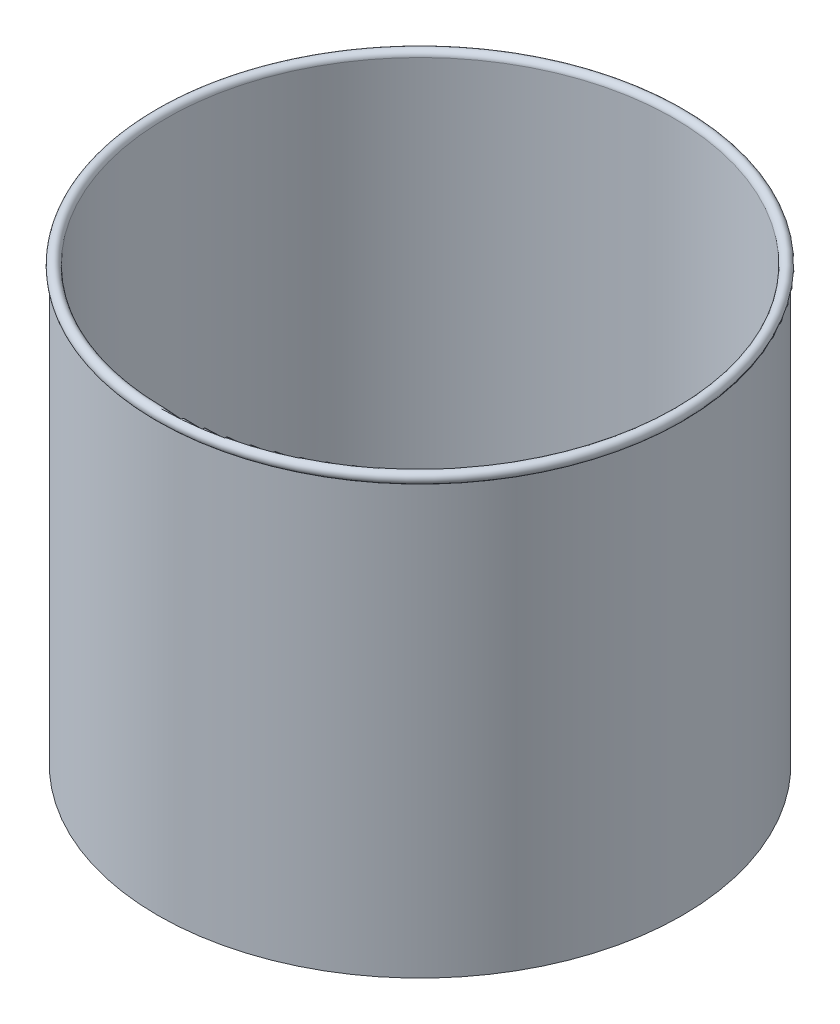
SolidWorks part; units mm, degrees
material "1023 Carbon Steel Sheet (SS)"
ref_plane "Front Plane" through (0, 0, 0) normal (0, 0, 1) x (1, 0, 0)
ref_plane "Top Plane" through (0, 0, 0) normal (0, 1, 0) x (1, 0, 0)
ref_plane "Right Plane" through (0, 0, 0) normal (1, 0, 0) x (0, 0, -1)
sketch "Sketch3" plane through (0, 0, 0) normal (0, 1, 0) x (1, 0, 0)
  circle A0 centre (0, 0) radius 122.5
  dimension "D1" = 245
extrude "Extrude-Thin1" add sketch "Sketch3" along normal blind 192 thin thin type one direction reverse wall 4
extrude "Boss-Extrude4" add sketch "Sketch3<3>" against normal blind 10 separate body
sketch "Sketch3<3>" plane through (0, 0, 0) normal (0, 1, 0) x (1, 0, 0) same geometry as "Sketch3"
sketch "Sketch9" plane through (0, 0, 0) normal (0, 0, 1) x (1, 0, 0)
  line L0 (0, -1000) -> (0, 49000) construction
  line L6 (121.3057, 189.3516) -> (121.3057, 192)
  line L7 (122.5, 192) -> (-122.5, 192) construction
  line L8 (121.3057, 192) -> (118.5, 192)
  arc A0 (118.5, 192) -> (121.3057, 189.3516) centre (120.9944, 191.8321) cw
  dimension "D4" = 2.5
revolve "Revolve2" add sketch "Sketch9" angle 360 about L0
sketch "Sketch11" plane through (0, 0, 0) normal (0, 1, 0) x (1, 0, 0)
  circle A0 centre (0, 0) radius 5
  dimension "D1" = 10
extrude "Boss-Extrude5" add sketch "Sketch11" along normal blind 20
sketch "Sketch13" plane through (0, -10, 0) normal (0, -1, 0) x (1, 0, 0)
  circle A0 centre (0, 0) radius 27.5
  dimension "D1" = 55
extrude "Cut-Extrude2" cut sketch "Sketch13" against normal blind 9
sketch "Sketch15" plane through (0, -1, 0) normal (0, -1, 0) x (1, 0, 0)
  line L0 (0, -15) -> (0, -27.1243)
  line L1 (6.4478, -13.5435) -> (4.3017, -26.781)
  arc A0 (0, -15) -> (6.4478, -13.5435) centre (0, 0) ccw
  arc A7 (0, -27.1243) -> (4.3017, -26.781) centre (0, 0) ccw
ref_plane "Plane2" through (0, -9, 0) normal (0, 1, 0) x (1, 0, 0)
sketch "Sketch19" plane through (0, -9, 0) normal (0, 1, 0) x (1, 0, 0)
  line L0 (-0.4301, 27.0941) -> (-0.4301, 14.994)
  line L1 (0.4997, 14.9919) -> (0.4997, 27.1593)
  line L2 (0.4997, 27.1593) -> (-0.4301, 27.0941)
  arc A0 (-0.4301, 14.994) -> (0.4997, 14.9919) centre (0, -0.3676) cw
loft "Loft10" add profiles "Sketch15", "Sketch19"
sketch "Sketch20" plane through (0, 0, 0) normal (0, 0, 1) x (1, 0, 0)
  line L0 (0, -1000) -> (0, 49000) construction
pattern_circular "CirPattern1" count 6 over 360 about axis through (0, -1000, 0) along (0, 1, 0) of "Loft10"
sketch "Sketch23" plane through (0, -1, 0) normal (0, -1, 0) x (-1, 0, 0)
  circle A0 centre (0, 0) radius 12.5
  dimension "D1" = 25
extrude "Extrude-Thin2" add sketch "Sketch23" along normal blind 9 thin thin type one direction reverse wall 2
